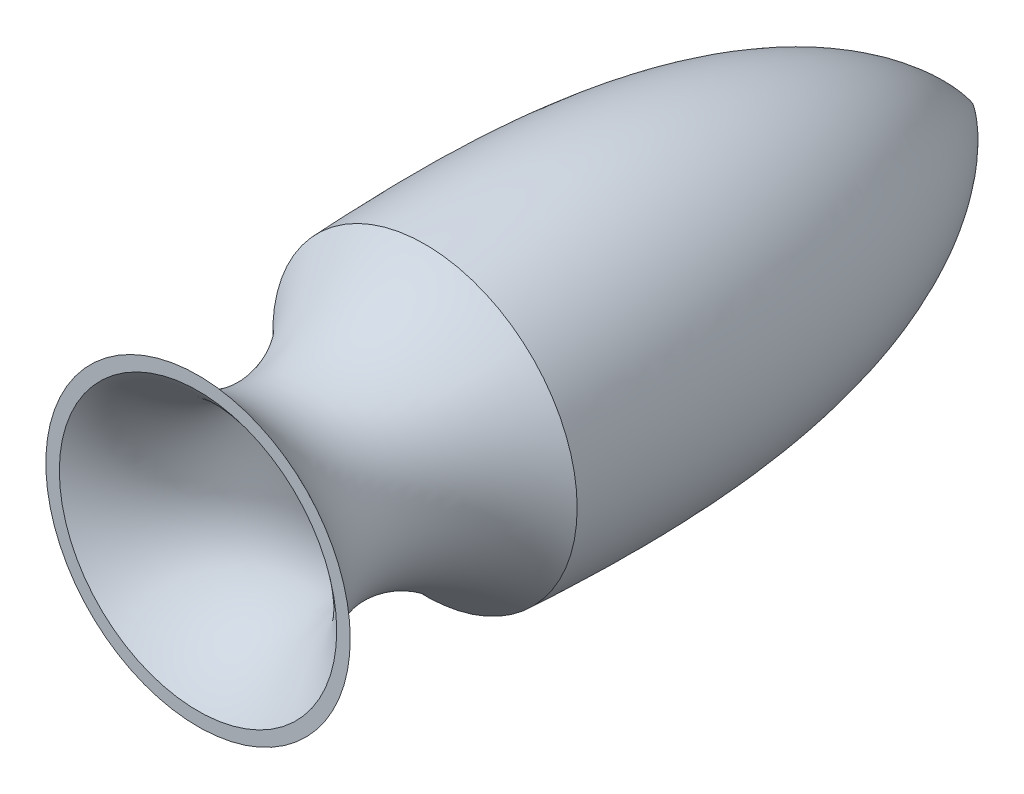
SolidWorks part; units mm, degrees
ref_plane "Front Plane" through (0, 0, 0) normal (0, 0, 1) x (1, 0, 0)
ref_plane "Top Plane" through (0, 0, 0) normal (0, 1, 0) x (1, 0, 0)
ref_plane "Right Plane" through (0, 0, 0) normal (1, 0, 0) x (0, 0, -1)
sketch "Sketch2" plane through (0, 0, 0) normal (0, 1, 0) x (1, 0, 0)
  line L0 (0, -1003.5036) -> (0, 3996.4964)
  line L2 (982.338, -1003.5036) -> (0, -1003.5036)
  spline S0 degree 3 poles (0, 3996.4964) (1048.8164, 3245.5059) (1027.8734, 1528.0927) (982.338, 461.0373) knots 0 0 0 0 1 1 1 1
  spline S1 degree 3 poles (982.338, 461.0373) (582.6651, 96.283) (312.3308, -560.6318) (982.338, -1003.5036) knots 0 0 0 0 1 1 1 1
  dimension "D1" = 5000
revolve "Revolve2" add sketch "Sketch2" angle 360 about L0
shell "Shell3" thickness 50 removed face at (982.338, 0, 1003.5036)
